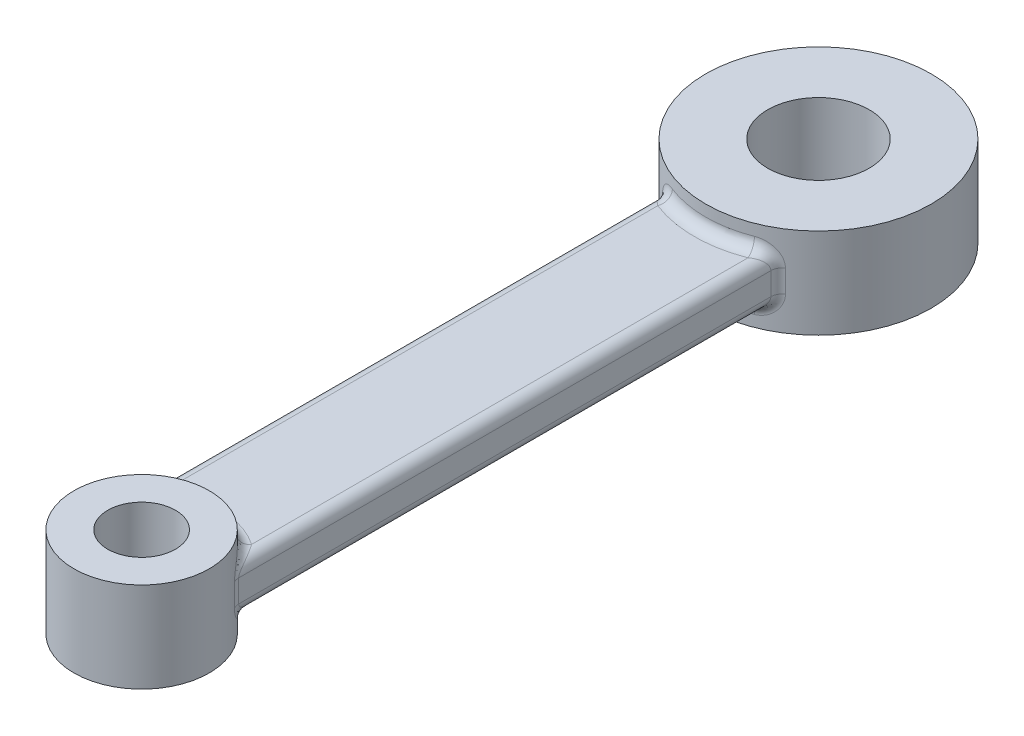
SolidWorks part; units mm, degrees
ref_plane "Front Plane" through (0, 0, 0) normal (0, 0, 1) x (1, 0, 0)
ref_plane "Top Plane" through (0, 0, 0) normal (0, 1, 0) x (1, 0, 0)
ref_plane "Right Plane" through (0, 0, 0) normal (1, 0, 0) x (0, 0, -1)
sketch "Sketch1" plane through (0, 0, 0) normal (0, 1, 0) x (1, 0, 0)
  line L1 (-2.5, 15) -> (2.5, 15)
  line L2 (-2.5, 15) -> (-2.5, -15)
  line L3 (-2.5, -15) -> (2.5, -15)
  line L4 (2.5, 15) -> (2.5, -15)
  line L5 (-2.5, 15) -> (2.5, -15) construction
  line L6 (-2.5, -15) -> (2.5, 15) construction
  point P0 (0, 0)
  dimension "D1" = 5
  dimension "D2" = 30
extrude "Boss-Extrude1" add sketch "Sketch1" along normal mid plane 2
sketch "Sketch2" plane through (0, 0, 0) normal (0, 1, 0) x (1, 0, 0)
  line L1 (2.5, 15) -> (-2.5, 15) construction
  line L2 (-2.5, -15) -> (2.5, -15) construction
  circle A0 centre (0, -15) radius 3
  circle A1 centre (0, 15) radius 5
  point P4 (0, 0)
  point P5 (0, 0)
  point P8 (0, -15.0728)
  point P9 (0, 0)
  point P12 (0, 15)
  point P14 (0, 0)
  point P15 (0, -14.7911)
  dimension "D1" = 6
  dimension "D2" = 10
extrude "Boss-Extrude2" add sketch "Sketch2" along normal mid plane 4
sketch "Sketch3" plane through (0, 0, 0) normal (0, 1, 0) x (1, 0, 0)
  circle A0 centre (0, -15) radius 1.5
  circle A1 centre (0, 15) radius 2.25
  dimension "D1" = 3
  dimension "D2" = 4.5
extrude "Cut-Extrude1" cut sketch "Sketch3" against normal mid plane 5
fillet "Fillet1" radius 0.5 4 edges at (-2.5, 1, 1.3359) (-2.5, -1, 1.3359) (2.5, -1, 1.3359) (2.5, 1, 1.3359)
fillet "Fillet2" radius 0.5 16 edges at (2.3376, 0.8688, -10.5801) (2.5, 0, -10.6699) (2.4123, -0.7829, -10.6204) (0, -1, -10) (-2.3376, -0.8688, -10.5801) (-2.5, 0, -10.6699) (-2.4123, 0.7829, -10.6204) (0, 1, -10) (-2.3986, 0.8019, 13.1981) (-2.5, 0, 13.3417) (-2.4553, -0.7066, 13.2762) (0, -1, 12) (2.3986, -0.8019, 13.1981) (2.5, 0, 13.3417) (2.4553, 0.7066, 13.2762) (0, 1, 12)
